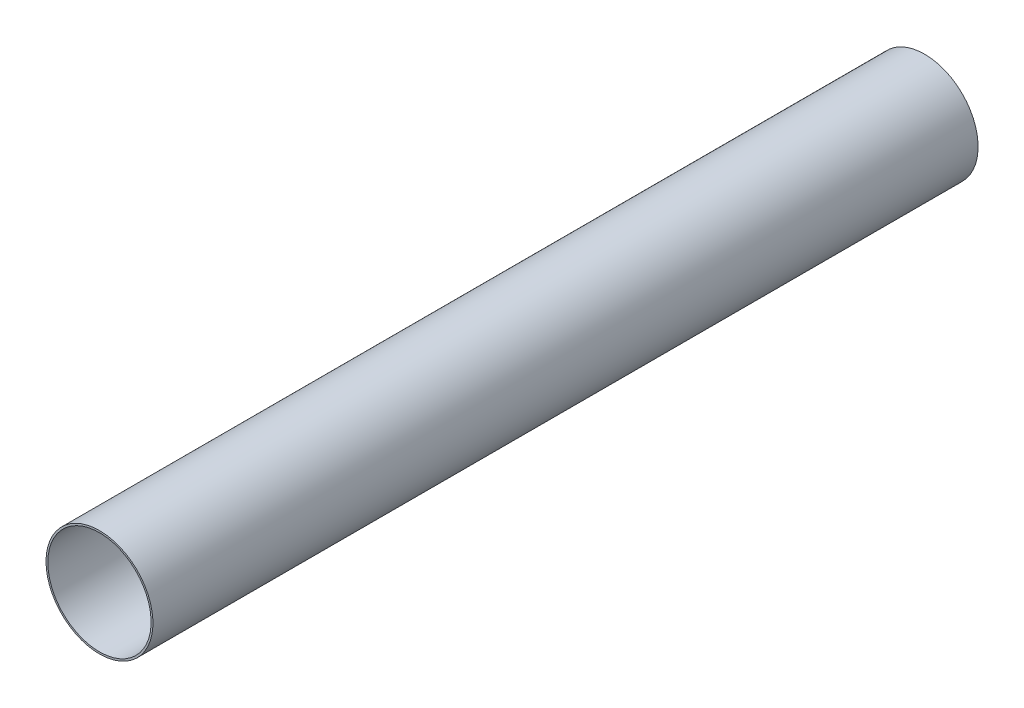
SolidWorks part; units mm, degrees
ref_plane "Plan de face" through (0, 0, 0) normal (0, 0, 1) x (1, 0, 0)
ref_plane "Plan de dessus" through (0, 0, 0) normal (0, 1, 0) x (1, 0, 0)
ref_plane "Plan de droite" through (0, 0, 0) normal (1, 0, 0) x (0, 0, -1)
sketch "Esquisse1" plane through (0, 0, 0) normal (0, 0, 1) x (1, 0, 0)
  circle A2 centre (0, 0) radius 79
  circle A3 centre (0, 0) radius 76.29
  dimension "D1" = 152.58
  dimension "D2" = 158
extrude "Boss.-Extru.1" add sketch "Esquisse1" along normal blind 1219.2 contours A2 | A3
